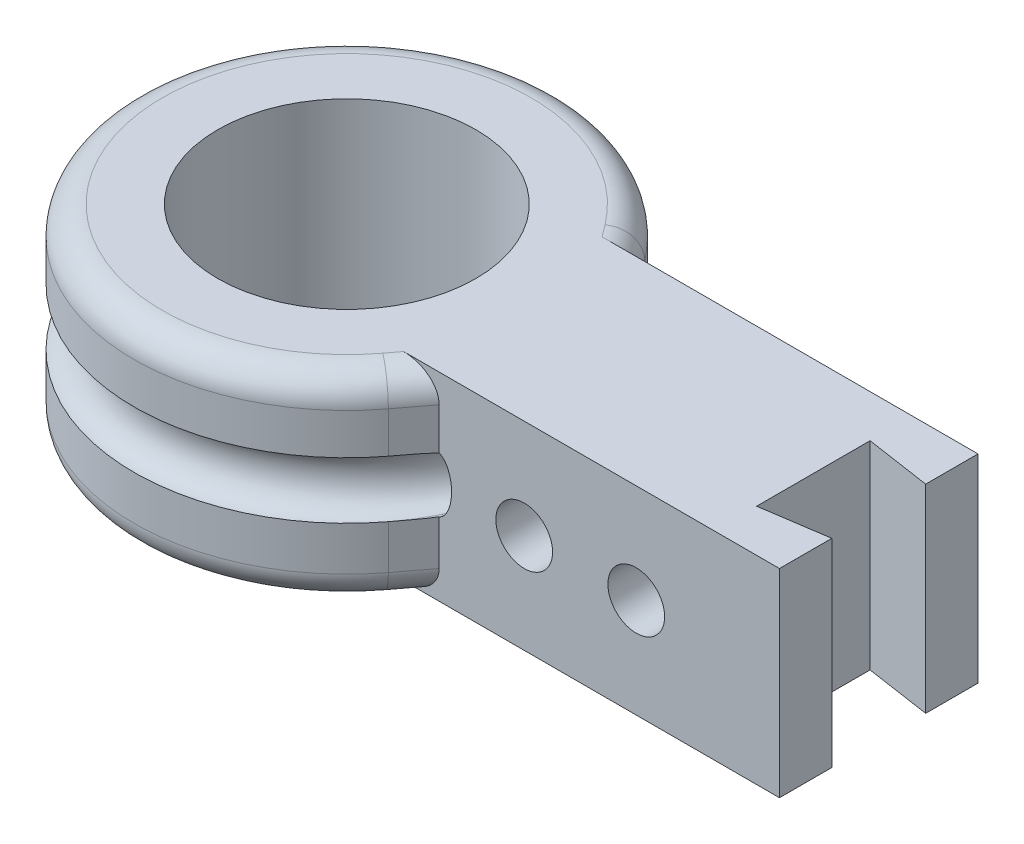
SolidWorks part; units mm, degrees
ref_plane "Front Plane" through (0, 0, 0) normal (0, 0, 1) x (1, 0, 0)
ref_plane "Top Plane" through (0, 0, 0) normal (0, 1, 0) x (1, 0, 0)
ref_plane "Right Plane" through (0, 0, 0) normal (1, 0, 0) x (0, 0, -1)
sketch "Sketch1" plane through (0, 0, 0) normal (0, 1, 0) x (1, 0, 0)
  line L0 (-10.3258, 0) -> (22.3498, 0) construction
  line L1 (6.7556, 3.5) -> (5.984, 4.5213)
  line L2 (6.7556, -3.5) -> (18.7556, -3.5)
  line L4 (6.7556, 3.5) -> (18.7556, 3.5)
  line L5 (18.7556, -3.5) -> (18.7556, -1.655)
  line L6 (6.7556, -3.5) -> (18.7556, 3.5) construction
  line L7 (6.7556, 3.5) -> (18.7556, -3.5) construction
  line L8 (6.7556, -3.5) -> (5.984, -4.5213)
  line L9 (18.7556, 1.655) -> (16.45, 2)
  line L13 (16.45, -2) -> (16.45, 2)
  line L16 (16.45, -2) -> (18.7556, -1.655)
  line L17 (18.7556, 1.655) -> (18.7556, 3.5)
  arc A0 (5.984, 4.5213) -> (5.984, -4.5213) centre (0, 0) ccw
  circle A1 centre (0, 0) radius 4.55
  point P4 (16.45, 0)
  point P5 (12.7556, 0)
  point P11 (18.5, 0)
  point P18 (18.7556, 1.655)
  point P19 (18.7556, 2.255)
  point P23 (18.7556, -1.655)
  dimension "D1" = 15
  dimension "D2" = 9.1
  dimension "D3" = 12
  dimension "D4" = 7
  dimension "D5" = 4
  dimension "D6" = 1.845
  dimension "D7" = 0.6
extrude "Boss-Extrude2" add sketch "Sketch1" along normal blind 7 contours A1 | L2 L5 L16 L13 L9 L17 L4 L1 A0 L8 region at (0, 0, 0)
sketch "Sketch2" plane through (0, 0, 0) normal (1, 0, 0) x (0, -1, 0)
  line L0 (0, -0.6001) -> (0, 7.5244) construction
  line L3 (-7.3353, 0) -> (0.2116, 0) construction
  line L4 (-7.3353, 7.5) -> (0.2244, 7.5) construction
  ellipse E0 centre (-3.5555, 7.5) end of major axis (-2.5555, 7.5) minor radius 0.8 (-4.5555, 7.5) -> (-2.5555, 7.5) ccw
  ellipse E1 centre (-3.5555, 7.5) end of major axis (-2.5555, 7.5) minor radius 0.5 (-2.5555, 7.5) -> (-4.5555, 7.5) ccw
  point P5 (-4.0532, 7.5)
  point P6 (-2.3212, 6.5715)
  point P20 (0, 7.5)
  dimension "D3" = 0.5
revolve "Cut-Revolve1" cut sketch "Sketch2" angle 360 about L3
sketch "Sketch3" plane through (0, 0, 3.5) normal (0, 0, 1) x (1, 0, 0)
  line L0 (18.7556, 3.5) -> (6.0558, 3.5) construction
  line L1 (18.7556, 7) -> (18.7556, 0) construction
  line L2 (16.7056, 7.1416) -> (16.7056, -0.1293) construction
  circle A2 centre (13.7056, 3.5) radius 1
  circle A3 centre (9.7556, 3.5) radius 1
  point P4 (14.7056, 3.5)
  point P5 (13.7056, 3.5)
  point P11 (9.7556, 3.5)
  point P13 (16.7056, 3.5)
  dimension "D1" = 2
  dimension "D3" = 3.95
  dimension "D2" = 3
  dimension "D4" = 2.05
extrude "Cut-Extrude1" cut sketch "Sketch3" against normal up to next contours A3 | A2
fillet "Fillet4" radius 1 6 edges at (6.3698, 0, -4.0107) (6.3698, 0, 4.0107) (6.3698, 7, -4.0107) (6.3698, 7, 4.0107) (-7.5, 0, 0) (-7.5, 7, 0)
